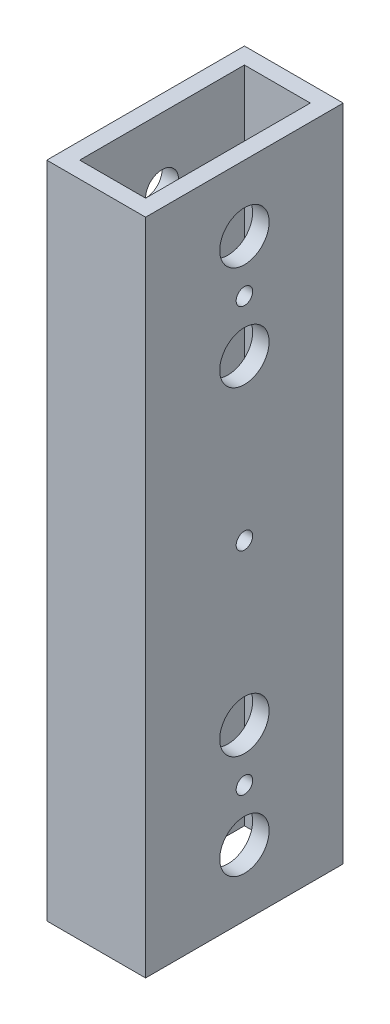
SolidWorks part; units mm, degrees
ref_plane "Front" through (0, 0, 0) normal (0, 0, 1) x (1, 0, 0)
ref_plane "Top" through (0, 0, 0) normal (0, 1, 0) x (1, 0, 0)
ref_plane "Right" through (0, 0, 0) normal (1, 0, 0) x (0, 0, -1)
sketch "Sketch1" plane through (0, 0, 0) normal (0, 1, 0) x (1, 0, 0)
  line L0 (3.175, 3.175) -> (15.875, 3.175)
  line L1 (0, 0) -> (19.05, 0)
  line L2 (0, 0) -> (0, 38.1)
  line L3 (0, 38.1) -> (19.05, 38.1)
  line L4 (19.05, 0) -> (19.05, 38.1)
  line L5 (15.875, 3.175) -> (15.875, 34.925)
  line L6 (3.175, 34.925) -> (15.875, 34.925)
  line L7 (3.175, 3.175) -> (3.175, 34.925)
  dimension "D1" = 38.1
  dimension "D2" = 19.05
  dimension "D3" = 3.175
extrude "Boss-Extrude1" add sketch "Sketch1" along normal blind 127
sketch "Sketch2" plane through (19.05, 0, 0) normal (1, 0, 0) x (0, 0, -1)
  line L0 (19.05, 0) -> (19.05, 12.7) construction
  line L1 (0, 0) -> (38.1, 0) construction
  line L2 (19.05, 12.7) -> (19.05, 32.7) construction
  line L3 (0, 63.5) -> (38.1, 63.5) construction
  line L4 (0, 127) -> (0, 0) construction
  line L5 (38.1, 127) -> (38.1, 0) construction
  line L6 (19.05, 114.3) -> (19.05, 94.3) construction
  circle A0 centre (19.05, 12.7) radius 3.175
  circle A1 centre (19.05, 32.7) radius 3.175
  circle A2 centre (19.05, 94.3) radius 3.175
  circle A3 centre (19.05, 114.3) radius 3.175
  dimension "D2" = 6.35
  dimension "D1" = 12.7
  dimension "D3" = 20
extrude "Cut-Extrude1" cut sketch "Sketch2" against normal through all
sketch "Sketch3" plane through (19.05, 0, 0) normal (1, 0, 0) x (0, 0, -1)
  circle A0 centre (19.05, 114.3) radius 4.7625
  circle A1 centre (19.05, 94.3) radius 4.7625
  circle A2 centre (19.05, 32.7) radius 4.7625
  circle A4 centre (19.05, 12.7) radius 4.7625
  circle A5 centre (19.05, 32.7) radius 3.175 construction
  circle A6 centre (19.05, 12.7) radius 3.175 construction
  circle A7 centre (19.05, 94.3) radius 3.175 construction
  circle A8 centre (19.05, 114.3) radius 3.175 construction
  dimension "D1" = 9.525
extrude "Cut-Extrude2" cut sketch "Sketch3" against normal up to next
sketch "Sketch4" plane through (19.05, 0, 0) normal (1, 0, 0) x (0, 0, -1)
  line L0 (19.05, 27.9375) -> (19.05, 17.4625) construction
  line L1 (0, 63.5) -> (38.1, 63.5) construction
  line L2 (0, 127) -> (0, 0) construction
  line L3 (38.1, 127) -> (38.1, 0) construction
  circle A0 centre (19.05, 32.7) radius 4.7625 construction
  circle A1 centre (19.05, 12.7) radius 4.7625 construction
  circle A2 centre (19.05, 22.7) radius 1.5875
  circle A3 centre (19.05, 63.5) radius 1.5875
  circle A4 centre (19.05, 104.3) radius 1.5875
  dimension "D1" = 3.175
  dimension "D2" = 40.8
extrude "UChan_Mount" cut sketch "Sketch4" against normal through all
sketch "Sketch5" plane through (0, 0, 0) normal (-1, 0, 0) x (0, 0, 1)
  circle A0 centre (-19.05, 104.3) radius 4.7625
  circle A1 centre (-19.05, 63.5) radius 4.7625
  circle A2 centre (-19.05, 22.7) radius 4.7625
  circle A3 centre (-19.05, 22.7) radius 1.5875 construction
  circle A4 centre (-19.05, 63.5) radius 1.5875 construction
  circle A5 centre (-19.05, 104.3) radius 1.5875 construction
  dimension "D1" = 9.525
extrude "Cut-Extrude4" cut sketch "Sketch5" against normal up to next
ref_plane "Mid_Plane" through (0, 0, -19.05) normal (0, 0, -1) x (-1, 0, 0)
